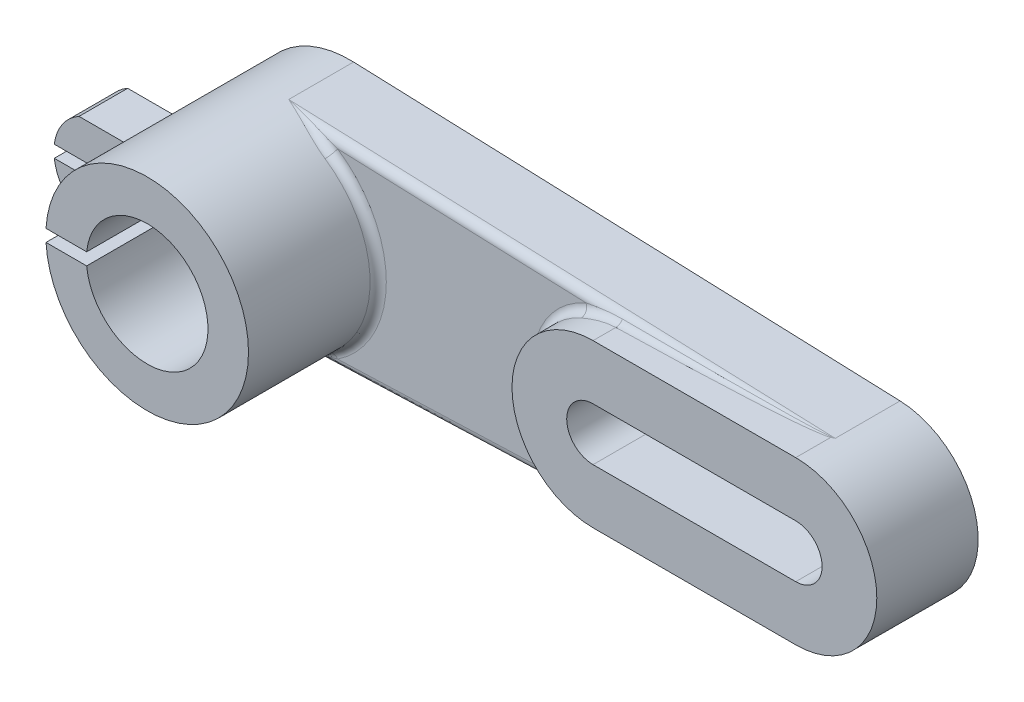
SolidWorks part; units mm, degrees
ref_plane "Ön Düzlem" through (0, 0, 0) normal (0, 0, 1) x (1, 0, 0)
ref_plane "Üst Düzlem" through (0, 0, 0) normal (0, 1, 0) x (1, 0, 0)
ref_plane "Sağ Düzlem" through (0, 0, 0) normal (1, 0, 0) x (0, 0, -1)
sketch "Çizim1" plane through (0, 0, 0) normal (0, 0, 1) x (1, 0, 0)
  line L0 (0.9259, 24.9828) -> (135.7407, 19.9863)
  line L1 (0.9259, -24.9828) -> (135.7407, -19.9863)
  line L2 (-27.9465, 0) -> (25, 0) construction
  line L3 (155, 0) -> (173.7093, 0) construction
  arc A0 (0.9259, 24.9828) -> (0.9259, -24.9828) centre (0, 0) ccw
  arc A1 (135.7407, -19.9863) -> (135.7407, 19.9863) centre (135, 0) ccw
  circle A2 centre (0, 0) radius 15
  dimension "D1" = 50
  dimension "D2" = 40
  dimension "D4" = 30
  dimension "D3" = 135
extrude "Yükseklik-Ekstrüzyon1" add sketch "Çizim1" along normal blind 18
sketch "Çizim2" plane through (0, 0, 18) normal (0, 0, 1) x (1, 0, 0)
  line L0 (85, 0) -> (135, 0) construction
  line L1 (85, 20) -> (135, 20)
  line L2 (85, -20) -> (135, -20)
  circle A0 centre (0, 0) radius 25
  circle A1 centre (0, 0) radius 15
  arc A2 (85, 20) -> (85, -20) centre (85, 0) ccw
  arc A3 (135, -20) -> (135, 20) centre (135, 0) ccw
  point P7 (110, 0)
  arc M1 (0.9259, 24.9828) -> (0.9259, -24.9828) centre (0, 0) ccw
  circle M5 centre (0, 0) radius 15
  dimension "D3" = 20
  dimension "D1" = 50
  dimension "D2" = 135
sketch "Çizim3" plane through (0, 0, 18) normal (0, 0, 1) x (1, 0, 0)
  line L0 (85, 20) -> (135, 20) construction
  line L1 (85, -20) -> (135, -20) construction
  line L2 (85, 20) -> (135, 20)
  line L3 (85, -20) -> (135, -20)
  arc A0 (135, -20) -> (135, 20) centre (135, 0) ccw construction
  arc A1 (85, 20) -> (85, -20) centre (85, 0) ccw construction
  arc A2 (135, -20) -> (135, 20) centre (135, 0) ccw
  arc A3 (85, 20) -> (85, -20) centre (85, 0) ccw
extrude "Yükseklik-Ekstrüzyon2" add sketch "Çizim2" along normal blind 32 contours A0 M1 M5 region at (17.4929, -16.8566, 18)
extrude "Yükseklik-Ekstrüzyon3" add sketch "Çizim3" along normal blind 7
sketch "Çizim4" plane through (0, 0, 25) normal (0, 0, 1) x (1, 0, 0)
  line L0 (85, 0) -> (135, 0) construction
  line L1 (85, 6.5) -> (135, 6.5)
  line L2 (85, -6.5) -> (135, -6.5)
  arc A0 (85, 6.5) -> (85, -6.5) centre (85, 0) ccw
  arc A1 (135, -6.5) -> (135, 6.5) centre (135, 0) ccw
  point P3 (110, 0)
  dimension "D1" = 13
  dimension "D2" = 50
  dimension "D3" = 135
extrude "Kes-Ekstrüzyon1" cut sketch "Çizim4" against normal up to surface (25 mm away) up to face at (66.6667, 0, 0)
ref_plane "Düzlem1" through (-42, 0, 0) normal (1, 0, 0) x (0, 0, -1)
sketch "Çizim7" plane through (-42, 0, 0) normal (1, 0, 0) x (0, 0, -1)
  line L0 (-25, 25) -> (-25, -25) construction
  line L1 (0, 25) -> (-50, 25) construction
  line L2 (-50, -25) -> (0, -25) construction
  line L3 (0, 0) -> (-50, 0) construction
  line L4 (-50, 25) -> (-50, -25) construction
  line L6 (-19, -10.5) -> (-31, -10.5)
  line L7 (-19, -10.5) -> (-19, 10.5)
  line L8 (-19, 10.5) -> (-31, 10.5)
  line L9 (-31, -10.5) -> (-31, 10.5)
  line L10 (-19, -10.5) -> (-31, 10.5) construction
  line L11 (-19, 10.5) -> (-31, -10.5) construction
  point P11 (-25, 0)
  dimension "D1" = 21
  dimension "D2" = 12
extrude "Yükseklik-Ekstrüzyon4" add sketch "Çizim7" along normal up to surface (31.2879 mm away) up to face at (15, 0, 0)
sketch "Çizim8" plane through (0, 0, 31) normal (0, 0, 1) x (1, 0, 0)
  line L0 (-22.6881, -10.5) -> (-42, -10.5) construction
  line L1 (-42, 10.5) -> (-42, -10.5) construction
  line L2 (-22.6881, 10.5) -> (-42, 10.5) construction
  line L3 (-35.8095, -10.5) -> (-42, -10.5)
  line L4 (-42, 10.5) -> (-42, -10.5)
  line L5 (-35.8095, 10.5) -> (-42, 10.5)
  circle A0 centre (-30, 0) radius 3.5
  arc A1 (-35.8095, 10.5) -> (-35.8095, -10.5) centre (-30, 0) ccw
  line M3 (-42, -10.5) -> (-22.6881, -10.5)
  line M5 (-22.6881, 10.5) -> (-42, 10.5)
  line M7 (-42, 10.5) -> (-42, -10.5)
  dimension "D1" = 7
  dimension "D2" = 30
extrude "Kes-Ekstrüzyon2" cut sketch "Çizim8" against normal up to surface (12 mm away) contours A1 M5 M7 | A0 | A1 L4 M3 | L4 L3 A1 L5 region at (-40.2687, 8.029, 31) region at (-40.2687, -8.029, 31) region at (-30, 0, 31) up to face at (-32.922, 0, 19)
sketch "Çizim9" plane through (0, 0, 0) normal (0, 0, 1) x (1, 0, 0)
  line L1 (7.963, -1.5) -> (-43.5337, -1.5)
  line L2 (7.963, -1.5) -> (7.963, 1.5)
  line L3 (7.963, 1.5) -> (-43.5337, 1.5)
  line L4 (-43.5337, -1.5) -> (-43.5337, 1.5)
  point P0 (0, 0)
  point P6 (7.7931, 1.5)
  point P7 (-7.963, -1.5)
  dimension "D1" = 3
extrude "Kes-Ekstrüzyon3" cut sketch "Çizim9" along normal up to surface (50 mm away) up to face at (15, 0, 50)
fillet "Radyus2" radius 2 1 edges at (68.3333, 22.4846, 18)
fillet "Radyus3" radius 2 7 edges at (24.4949, -5, 18) (65.018, -0.8472, 18) (118.5889, 20, 17.4491) (6.8866, 24.0328, 17.5439) (68.3333, -22.4846, 18)
